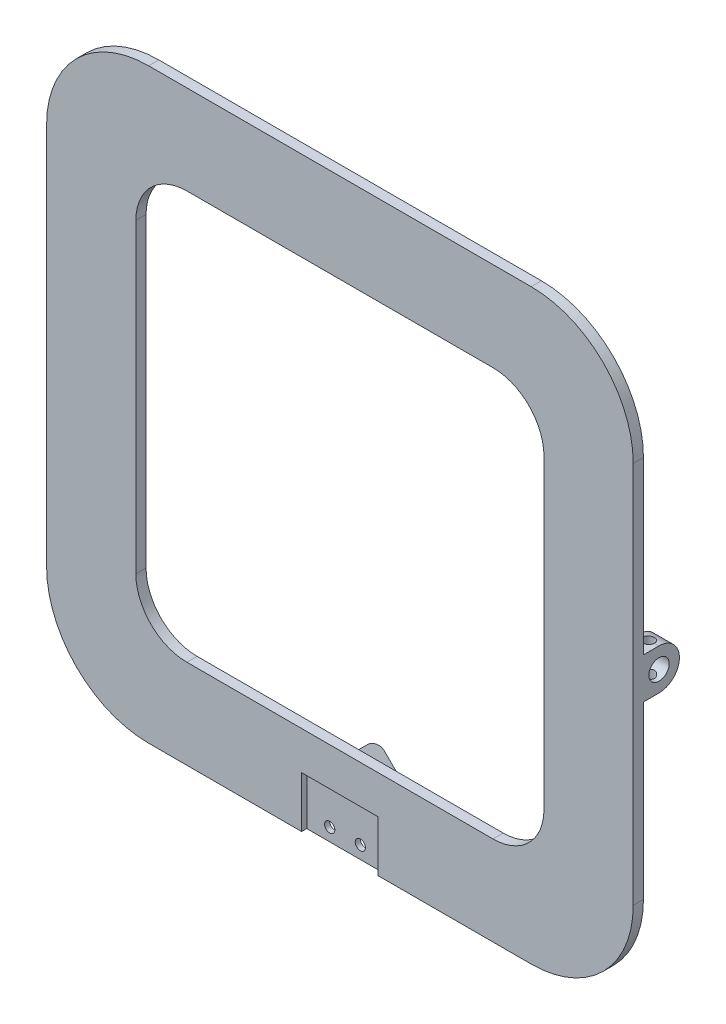
SolidWorks part; units mm, degrees
ref_plane "Płaszczyzna przednia" through (0, 0, 0) normal (0, 0, 1) x (1, 0, 0)
ref_plane "Płaszczyzna górna" through (0, 0, 0) normal (0, 1, 0) x (1, 0, 0)
ref_plane "Płaszczyzna prawa" through (0, 0, 0) normal (1, 0, 0) x (0, 0, -1)
sketch "Szkic1" plane through (0, 0, 0) normal (0, 0, 1) x (1, 0, 0)
  line L0 (0, -57.5) -> (115, -57.5) construction
  line L1 (0, 0) -> (115, 0)
  line L2 (0, 0) -> (0, -115)
  line L3 (0, -115) -> (115, -115)
  line L4 (115, 0) -> (115, -115)
  dimension "D1" = 115
  dimension "D2" = 115
extrude "Dodanie-wyciągnięcie1" add sketch "Szkic1" along normal blind 2
sketch "Szkic3" plane through (115, 0, 0) normal (1, 0, 0) x (0, 0, -1)
  line L0 (0, -115) -> (0, 0) construction
  line L1 (0, -53.5) -> (3.0506, -53.5)
  line L2 (0, -53.5) -> (0, -61.5)
  line L3 (0, -61.5) -> (3.0506, -61.5)
  line L6 (-2, -115) -> (0, -115) construction
  arc A0 (3.0506, -61.5) -> (3.0506, -53.5) centre (3.0506, -57.5) ccw
  dimension "D1" = 8
  dimension "D2" = 53.5
extrude "Dodanie-wyciągnięcie2" add sketch "Szkic3" against normal blind 4
ref_plane "Płaszczyzna1" through (57.5, 0, 0) normal (1, 0, 0) x (0, 0, -1)
mirror "Lustro1" about plane through (57.5, 0, 0) normal (1, 0, 0) of "Dodanie-wyciągnięcie2"
sketch "Szkic5" plane through (115, 0, 0) normal (1, 0, 0) x (0, 0, -1)
  circle A0 centre (3.0506, -57.5) radius 2
  arc A1 (3.0506, -61.5) -> (3.0506, -53.5) centre (3.0506, -57.5) ccw construction
  dimension "D1" = 4
extrude "Wytnij-wyciągnięcie1" cut sketch "Szkic5" against normal through all
sketch "Szkic6" plane through (0, 0, 2) normal (0, 0, 1) x (1, 0, 0)
  line L0 (0, 0) -> (0, -115) construction
  line L2 (0, -115) -> (115, -115) construction
  circle A0 centre (54.5, -112.5) radius 1
  circle A1 centre (60.5, -112.5) radius 1
  dimension "D1" = 2
  dimension "D2" = 2
  dimension "D5" = 2.5
  dimension "D6" = 2.5
  dimension "D3" = 6
  dimension "D4" = 54.5
extrude "Wytnij-wyciągnięcie2" cut sketch "Szkic6" against normal blind 10
fillet "Zaokrąglenie1" radius 20 4 edges at (0, -115, 1) (115, -115, 1) (0, 0, 1) (115, 0, 1)
sketch "Szkic7" plane through (0, 0, 2) normal (0, 0, 1) x (1, 0, 0)
  line L0 (20, -115) -> (95, -115) construction
  line L1 (50, -115) -> (65, -115)
  line L2 (50, -115) -> (50, -105)
  line L3 (50, -105) -> (65, -105)
  line L4 (65, -115) -> (65, -105)
  line L5 (0, -20) -> (0, -95) construction
  dimension "D1" = 10
  dimension "D2" = 15
  dimension "D3" = 50
extrude "Wytnij-wyciągnięcie3" cut sketch "Szkic7" against normal blind 1
sketch "Szkic8" plane through (0, 0, 0) normal (0, 0, -1) x (-1, 0, 0)
  line L0 (0, -20) -> (0, -53.5) construction
  line L1 (-87.5, -97.5) -> (-27.5, -97.5)
  line L2 (-97.5, -87.5) -> (-97.5, -27.5)
  line L3 (-87.5, -17.5) -> (-27.5, -17.5)
  line L4 (-17.5, -87.5) -> (-17.5, -27.5)
  line L5 (-97.5, -97.5) -> (-17.5, -17.5) construction
  line L6 (-97.5, -17.5) -> (-17.5, -97.5) construction
  line L7 (-95, 0) -> (-20, 0) construction
  arc A0 (-87.5, -97.5) -> (-97.5, -87.5) centre (-87.5, -87.5) cw
  arc A1 (-27.5, -97.5) -> (-17.5, -87.5) centre (-27.5, -87.5) ccw
  arc A2 (-27.5, -17.5) -> (-17.5, -27.5) centre (-27.5, -27.5) cw
  arc A3 (-97.5, -27.5) -> (-87.5, -17.5) centre (-87.5, -27.5) cw
  point P0 (-57.5, -57.5)
  dimension "D5" = 10
  dimension "D1" = 80
  dimension "D2" = 80
  dimension "D3" = 17.5
  dimension "D4" = 17.5
extrude "Wytnij-wyciągnięcie4" cut sketch "Szkic8" against normal blind 10
sketch "Szkic9" plane through (0, -53.5, 0) normal (0, 1, 0) x (1, 0, 0)
  line L0 (4, 3.0506) -> (0, 3.0506) construction
  circle A0 centre (2, 3.0506) radius 1.1
extrude "Wytnij-wyciągnięcie5" cut sketch "Szkic9" against normal through all
sketch "Szkic10" plane through (0, -53.5, 0) normal (0, 1, 0) x (1, 0, 0)
  line L0 (111, 3.0506) -> (115, 3.0506) construction
  circle A0 centre (113, 3.0506) radius 1.1
extrude "Wytnij-wyciągnięcie6" cut sketch "Szkic10" against normal blind 10
sketch "Szkic13" plane through (0, 0, 0) normal (0, 0, -1) x (-1, 0, 0)
  line L0 (-57.5, -115) -> (-57.5, -97.5) construction
  line L1 (-20, -115) -> (-95, -115) construction
  line L2 (-87.5, -97.5) -> (-27.5, -97.5) construction
  line L3 (-57.5, -106.25) -> (-66.25, -115) construction
  line L5 (-53.0806, -103.5983) -> (-60.1517, -110.6694)
  line L6 (-53.0806, -103.5983) -> (-54.8483, -101.8306)
  line L7 (-60.1517, -110.6694) -> (-61.9194, -108.9017)
  line L8 (-54.8483, -101.8306) -> (-61.9194, -108.9017)
  line L9 (-53.0806, -103.5983) -> (-61.9194, -108.9017) construction
  line L10 (-60.1517, -110.6694) -> (-54.8483, -101.8306) construction
  dimension "D1" = 10
  dimension "D2" = 2.5
  dimension "D3" = 45
extrude "Dodanie-wyciągnięcie4" add sketch "Szkic13" along normal blind 8
sketch "Szkic14" plane through (-25.2589, -25.2589, 0) normal (-0.7071, -0.7071, 0) x (-0.7071, 0.7071, 0)
  line L0 (-120.7887, 0) -> (-110.7887, 0) construction
  line L1 (-112.7887, 0) -> (-118.7887, 0)
  line L2 (-112.7887, 0) -> (-112.7887, 6)
  line L3 (-112.7887, 6) -> (-118.7887, 6)
  line L4 (-118.7887, 0) -> (-118.7887, 6)
  line L5 (-120.7887, 8) -> (-110.7887, 8) construction
  line L6 (-110.7887, 8) -> (-110.7887, 0) construction
  line L7 (-120.7887, 8) -> (-120.7887, 0) construction
  dimension "D1" = 2
  dimension "D2" = 2
  dimension "D3" = 2
extrude "Wytnij-wyciągnięcie8" cut sketch "Szkic14" against normal blind 8
fillet "Zaokrąglenie3" radius 2 4 edges at (59.6213, -108.3713, -6) (55.3787, -104.1287, -6) (61.0355, -109.7855, -8) (53.9645, -102.7145, -8)
sketch "Szkic15" plane through (0, 0, 0) normal (0, 0, -1) x (-1, 0, 0)
  line L0 (-109.1421, -109.1421) -> (-95, -95) construction
  line L1 (-104.6976, -106.4654) -> (-106.4654, -104.6976)
  line L2 (-104.6976, -106.4654) -> (-97.6265, -99.3943)
  line L3 (-106.4654, -104.6976) -> (-99.3943, -97.6265)
  line L4 (-97.6265, -99.3943) -> (-99.3943, -97.6265)
  line L5 (-104.6976, -106.4654) -> (-99.3943, -97.6265) construction
  line L6 (-106.4654, -104.6976) -> (-97.6265, -99.3943) construction
  arc A0 (-115, -95) -> (-95, -115) centre (-95, -95) ccw construction
  point P12 (-102.0459, -102.0459)
  dimension "D1" = 10
  dimension "D2" = 2.5
  dimension "D3" = 0
  dimension "805" = 8.5
extrude "Dodanie-wyciągnięcie5" add sketch "Szkic15" along normal blind 8
sketch "Szkic16" plane through (-0.8839, -0.8839, 0) normal (-0.7071, -0.7071, 0) x (-0.7071, 0.7071, 0)
  line L0 (-149.3148, 0) -> (-139.3148, 0) construction
  line L1 (-149.3148, 8) -> (-139.3148, 8) construction
  line L2 (-147.3148, 6) -> (-141.3148, 6)
  line L3 (-147.3148, 6) -> (-147.3148, 0)
  line L4 (-147.3148, 0) -> (-141.3148, 0)
  line L5 (-141.3148, 6) -> (-141.3148, 0)
  line L6 (-149.3148, 8) -> (-149.3148, 0) construction
  line L7 (-139.3148, 8) -> (-139.3148, 0) construction
  dimension "D1" = 2
  dimension "D2" = 2
  dimension "D3" = 2
extrude "Wytnij-wyciągnięcie9" cut sketch "Szkic16" against normal blind 8
fillet "Zaokrąglenie5" radius 2 4 edges at (99.9246, -99.9246, -6) (104.1673, -104.1673, -6) (98.5104, -98.5104, -8) (105.5815, -105.5815, -8)
pattern_linear "Szyk liniowy1" count 2 spacing 45 along (0, 1, 0) of "Wytnij-wyciągnięcie9", "Dodanie-wyciągnięcie5", "Zaokrąglenie5"
